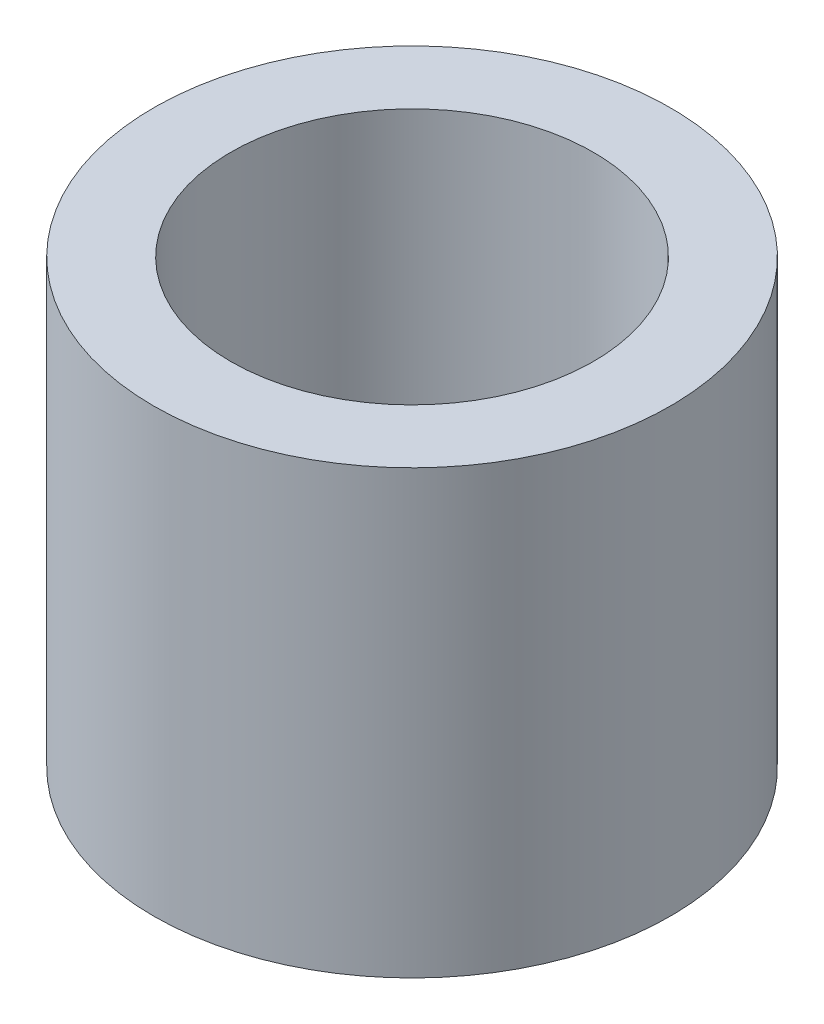
SolidWorks part; units mm, degrees
ref_plane "Front Plane" through (0, 0, 0) normal (0, 0, 1) x (1, 0, 0)
ref_plane "Top Plane" through (0, 0, 0) normal (0, 1, 0) x (1, 0, 0)
ref_plane "Right Plane" through (0, 0, 0) normal (1, 0, 0) x (0, 0, -1)
sketch "Sketch1" plane through (0, 0, 0) normal (0, 1, 0) x (1, 0, 0)
  circle A0 centre (0, 0) radius 22.5
  dimension "SLEEVE_OD" = 45
extrude "Boss-Extrude1" add sketch "Sketch1" along normal blind 38.4787
sketch "Sketch2" plane through (0, 0, 0) normal (0, 1, 0) x (1, 0, 0)
  circle A0 centre (0, 0) radius 15.7914
  dimension "BORE_D" = 31.5828
extrude "Cut-Extrude1" cut sketch "Sketch2" along normal through all
chamfer "Chamfer1" distance 3.4959 angle 45 rebuild error yes
